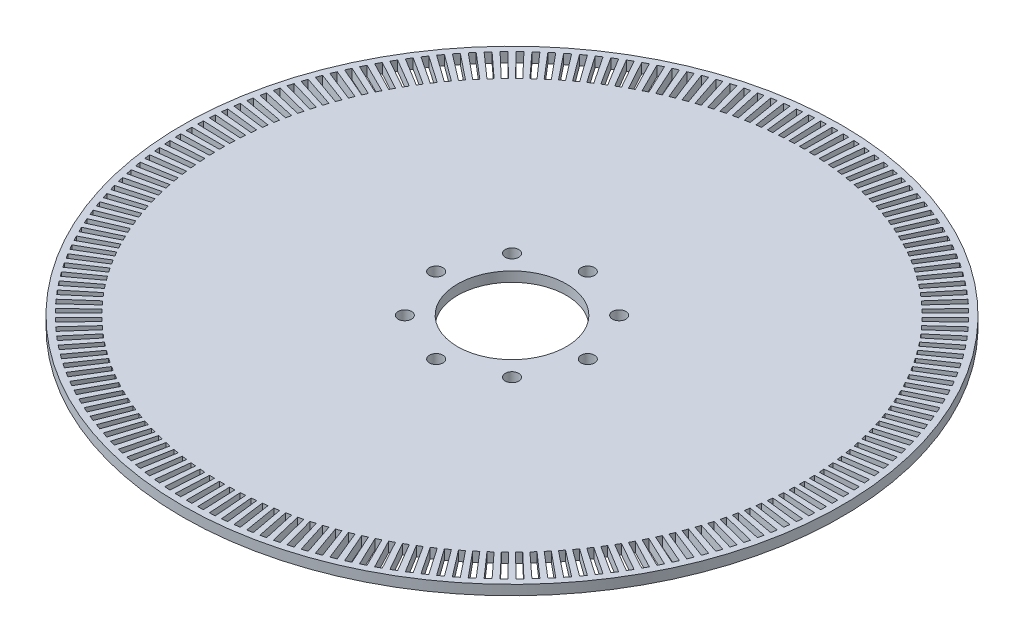
SolidWorks part; units mm, degrees
ref_plane "Front Plane" through (0, 0, 0) normal (0, 0, 1) x (1, 0, 0)
ref_plane "Top Plane" through (0, 0, 0) normal (0, 1, 0) x (1, 0, 0)
ref_plane "Right Plane" through (0, 0, 0) normal (1, 0, 0) x (0, 0, -1)
sketch "Sketch1" plane through (0, 0, 0) normal (0, 1, 0) x (1, 0, 0)
  circle A0 centre (0, 0) radius 16.5
  circle A1 centre (0, 0) radius 100
  dimension "D1" = 200
  dimension "D2" = 33
extrude "Boss-Extrude1" add sketch "Sketch1" along normal blind 3
sketch "Sketch2" plane through (0, 3, 0) normal (0, 1, 0) x (1, 0, 0)
  circle A0 centre (23, 0) radius 2.05
  dimension "D1" = 4.1
  dimension "D2" = 23
extrude "Cut-Extrude1" cut sketch "Sketch2" against normal through all
pattern_circular "CirPattern1" count 8 over 360 about axis through (0, 0, 0) along (0, 1, 0) of "Cut-Extrude1"
sketch "Sketch3" plane through (0, 3, 0) normal (0, 1, 0) x (1, 0, 0)
  line L0 (0, 0) -> (100, 0) construction
  line L3 (0, 0) -> (99.9962, 0.8727) construction
  line L4 (0, 0) -> (99.9962, -0.8727) construction
  line L5 (87.9966, 0.7679) -> (97.9963, 0.8552)
  line L6 (87.9966, -0.7679) -> (97.9963, -0.8552)
  circle A3 centre (0, 0) radius 100 construction
  arc A4 (87.9966, 0.7679) -> (87.9966, -0.7679) centre (0, 0) cw
  arc A5 (97.9963, -0.8552) -> (97.9963, 0.8552) centre (0, 0) ccw
  dimension "D3" = 88
  dimension "D4" = 98
  dimension "D1" = 1
  dimension "D2" = 0.5
extrude "Cut-Extrude2" cut sketch "Sketch3" against normal through all
pattern_circular "CirPattern2" count 180 over 360 about axis through (0, 0, 0) along (0, 1, 0) of "Cut-Extrude2"
equation "\"D2@Sketch3\"=0.5*\"D1@Sketch3\""
